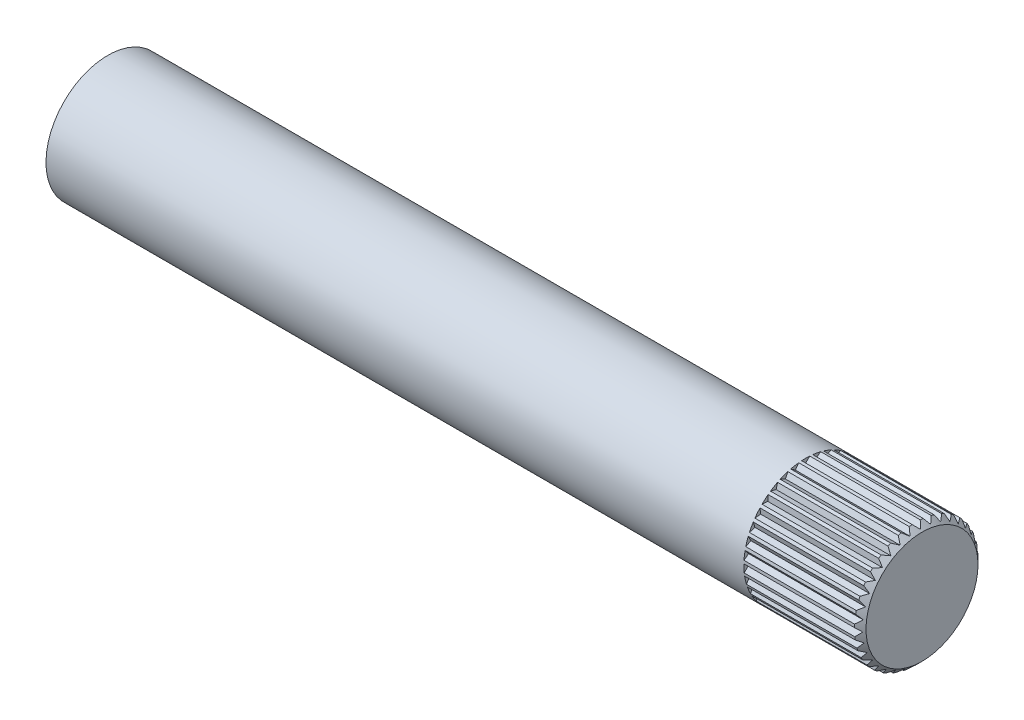
SolidWorks part; units mm, degrees
ref_plane "Front Plane" through (0, 0, 0) normal (0, 0, 1) x (1, 0, 0)
ref_plane "Top Plane" through (0, 0, 0) normal (0, 1, 0) x (1, 0, 0)
ref_plane "Right Plane" through (0, 0, 0) normal (1, 0, 0) x (0, 0, -1)
sketch "Sketch1" plane through (0, 0, 0) normal (1, 0, 0) x (0, 0, -1)
  circle A0 centre (0, 0) radius 6.75
  dimension "D1" = 13.5
extrude "Boss-Extrude1" add sketch "Sketch1" along normal blind 88.9
chamfer "Chamfer1" distance 0.635 angle 45 1 edges at (88.9, 0, -6.75)
sketch "Sketch2" plane through (88.9, 0, 0) normal (1, 0, 0) x (0, 0, -1)
  line L0 (-1.068, 7.3597) -> (0, 6.2918)
  line L1 (0, 6.2918) -> (1.068, 7.3597)
  line L2 (1.068, 7.3597) -> (-1.068, 7.3597)
  line L3 (0, 6.2918) -> (0, 8.242) construction
  dimension "D1" = 90
  dimension "D2" = 45
extrude "Cut-Extrude1" cut sketch "Sketch2" against normal blind 12.7
ref_axis "Axis1" through (88.9, 0, 0) along (-1, 0, 0)
pattern_circular "CirPattern2" count 35 over 360 about axis through (88.9, 0, 0) along (-1, 0, 0) of "Cut-Extrude1"
